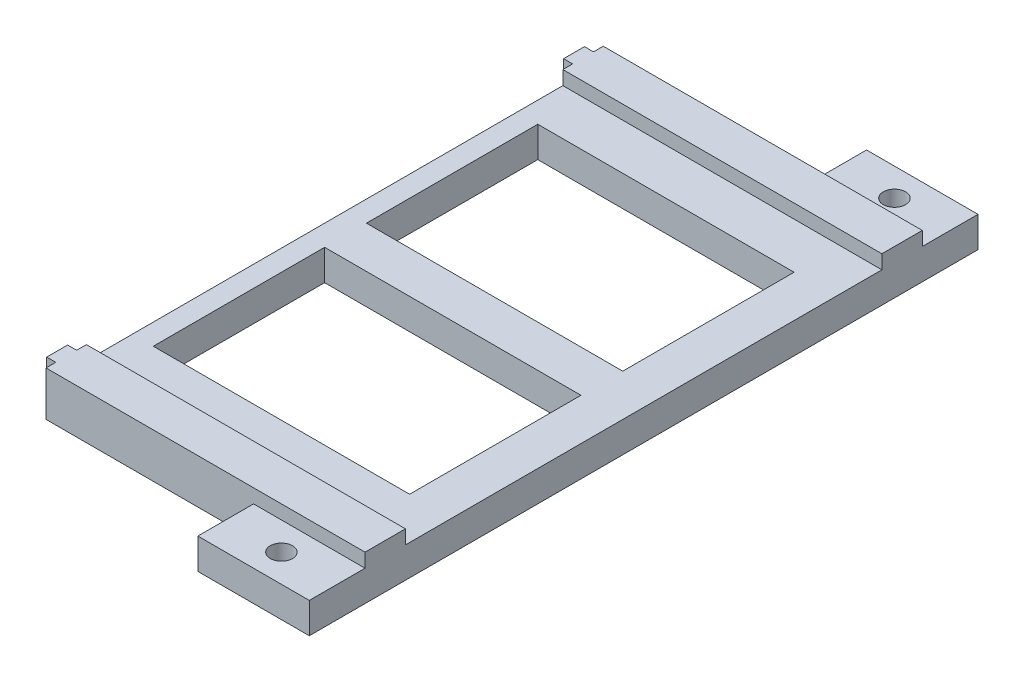
SolidWorks part; units mm, degrees
ref_plane "Front Plane" through (0, 0, 0) normal (0, 0, 1) x (1, 0, 0)
ref_plane "Top Plane" through (0, 0, 0) normal (0, 1, 0) x (1, 0, 0)
ref_plane "Right Plane" through (0, 0, 0) normal (1, 0, 0) x (0, 0, -1)
sketch "Sketch1" plane through (0, 0, 0) normal (0, 1, 0) x (1, 0, 0)
  line L1 (-184.5, -100) -> (184.5, -100)
  line L2 (-184.5, -100) -> (-184.5, 100)
  line L3 (-184.5, 100) -> (184.5, 100)
  line L4 (184.5, -100) -> (184.5, 100)
  line L5 (-184.5, -100) -> (184.5, 100) construction
  line L6 (-184.5, 100) -> (184.5, -100) construction
  point P0 (0, 0)
  dimension "D1" = 200
  dimension "353" = 369
extrude "Boss-Extrude1" add sketch "Sketch1" along normal blind 16
sketch "Sketch2" plane through (0, 16, 0) normal (0, 1, 0) x (1, 0, 0)
  line L0 (-184.5, -100) -> (184.5, -100) construction
  line L1 (-184.5, -100) -> (-155.6166, -100)
  line L2 (-184.5, -100) -> (-184.5, -36.5)
  line L3 (-184.5, -36.5) -> (-169.5, -36.5)
  line L4 (-169.5, -84) -> (-169.5, -36.5)
  line L5 (-184.5, 100) -> (-155.6166, 100)
  line L6 (-184.5, 100) -> (-184.5, 36.5)
  line L7 (-184.5, 36.5) -> (-169.5, 36.5)
  line L8 (-169.5, 84) -> (-169.5, 36.5)
  line L9 (-155.6166, 100) -> (-119.5, 100)
  line L11 (-169.5, 84) -> (-119.5, 84)
  line L12 (-119.5, 100) -> (-119.5, 84)
  line L13 (-155.6166, -100) -> (-119.5, -100)
  line L15 (-169.5, -84) -> (-119.5, -84)
  line L16 (-119.5, -100) -> (-119.5, -84)
  line L17 (-44.5, -100) -> (84.5, -100)
  line L18 (-44.5, -100) -> (-44.5, -84)
  line L19 (-44.5, -84) -> (84.5, -84)
  line L20 (84.5, -100) -> (84.5, -84)
  line L22 (-44.5, 100) -> (84.5, 100)
  line L23 (-44.5, 100) -> (-44.5, 84)
  line L24 (-44.5, 84) -> (84.5, 84)
  line L25 (84.5, 100) -> (84.5, 84)
  line L26 (184.5, -100) -> (184.5, 100) construction
  line L27 (184.5, 100) -> (-184.5, 100) construction
  point P28 (84.5, -92)
  dimension "D1" = 65
  dimension "D2" = 15
  dimension "D3" = 65
  dimension "D4" = 15
  dimension "D5" = 16
  dimension "D6" = 50
  dimension "D7" = 50
  dimension "D8" = 16
  dimension "D9" = 75
  dimension "D10" = 100
extrude "Boss-Extrude2" add sketch "Sketch2" along normal blind 12
sketch "Sketch3" plane through (0, 16, 0) normal (0, 1, 0) x (1, 0, 0)
  line L0 (-119.5, -84) -> (-169.5, -84) construction
  line L1 (-169.5, 84) -> (172.5, 84)
  line L2 (-169.5, 84) -> (-169.5, -84)
  line L3 (-169.5, -84) -> (172.5, -84)
  line L4 (172.5, 84) -> (172.5, -84)
  dimension "D1" = 342
extrude "Cut-Extrude1" cut sketch "Sketch3" against normal blind 5
sketch "Sketch4" plane through (0, 0, -100) normal (0, 0, -1) x (-1, 0, 0)
  line L0 (-84.5, 28) -> (44.5, 28) construction
  line L1 (-69.5, 16) -> (30.5, 16)
  line L2 (-69.5, 16) -> (-69.5, 28)
  line L3 (-69.5, 28) -> (30.5, 28)
  line L4 (30.5, 16) -> (30.5, 28)
  line L5 (-69.5, 16) -> (30.5, 28) construction
  line L6 (-69.5, 28) -> (30.5, 16) construction
  line L8 (-84.5, 28) -> (-84.5, 16) construction
  point P0 (-19.5, 22)
  dimension "D1" = 100
  dimension "D2" = 15
extrude "Boss-Extrude3" add sketch "Sketch4" along normal blind 60
sketch "Sketch8" plane through (0, 28, 0) normal (0, 1, 0) x (1, 0, 0)
  line L0 (-184.5, 36.5) -> (-169.5, 36.5)
  line L1 (-169.5, 36.5) -> (-169.5, 84)
  line L2 (-169.5, 84) -> (-119.5, 84)
  line L3 (-119.5, 84) -> (-119.5, 100)
  line L4 (-119.5, 100) -> (-184.5, 100)
  line L5 (-184.5, 100) -> (-184.5, 36.5)
extrude "Boss-Extrude5" add sketch "Sketch8" along normal blind 42
sketch "Sketch9" plane through (0, 70, 0) normal (0, 1, 0) x (1, 0, 0)
  line L0 (-119.5, 84) -> (-119.5, 70)
  line L1 (-119.5, 70) -> (-155.5, 70)
  line L2 (-155.5, 70) -> (-155.5, 35)
  line L3 (-155.5, 35) -> (-169.5, 35)
  line L4 (-169.5, 36.5) -> (-169.5, 84) construction
  line L5 (-169.5, 84) -> (-169.5, -84) construction
  line L6 (172.5, 84) -> (-169.5, 84) construction
  dimension "D1" = 14
  dimension "D2" = 14
extrude "Extrude-Thin1" add sketch "Sketch9" against normal blind 7 thin thin type one direction wall 10
sketch "Sketch11" plane through (0, 70, 0) normal (0, 1, 0) x (1, 0, 0)
  line L1 (-184.5, 100) -> (-44.5, 100)
  line L2 (-184.5, 100) -> (-184.5, -100)
  line L3 (-184.5, -100) -> (-44.5, -100)
  line L4 (-44.5, 100) -> (-44.5, -100)
extrude "Cut-Extrude5" cut sketch "Sketch11" against normal through all
sketch "Sketch13" plane through (0, 28, 0) normal (0, 1, 0) x (1, 0, 0)
  line L0 (-44.5, 96.22) -> (-44.5, 87.78)
  line L1 (-44.5, 100) -> (-44.5, 84) construction
  line L2 (-44.5, 87.78) -> (-52.3, 86.4046)
  line L3 (-52.3, 86.4046) -> (-52.3, 97.5954)
  line L4 (-52.3, 97.5954) -> (-44.5, 96.22)
  line L5 (-44.5, -87.78) -> (-44.5, -96.22)
  line L6 (-44.5, -96.22) -> (-52.5, -97.6306)
  line L7 (-52.5, -97.6306) -> (-52.5, -86.3694)
  line L8 (-52.5, -86.3694) -> (-44.5, -87.78)
  line L9 (-44.5, -84) -> (-44.5, -100) construction
  dimension "D1" = 3.78
  dimension "D2" = 3.78
  dimension "D3" = 7.8
  dimension "D4" = 80
  dimension "D5" = 80
  dimension "D6" = 3.78
  dimension "D7" = 3.78
  dimension "D8" = 80
  dimension "D9" = 8
  dimension "D10" = 80
extrude "Boss-Extrude6" add sketch "Sketch13" against normal through all
fillet "Fillet1" radius 1.5 8 edges at (-44.5, 14, 87.78) (-52.5, 14, 86.3694) (-52.5, 14, 97.6306) (-44.5, 14, 96.22) (-44.5, 14, -96.22) (-44.5, 14, -87.78) (-52.3, 14, -86.4046) (-52.3, 14, -97.5954)
sketch "Sketch14" plane through (0, 0, 0) normal (0, 0, 1) x (1, 0, 0)
  line L0 (84.5, 16) -> (184.5, 16) construction
  line L1 (84.5, 28) -> (-67.1004, 28)
  line L2 (84.5, 28) -> (84.5, 16)
  line L3 (84.5, 16) -> (-67.1004, 16)
  line L4 (-67.1004, 28) -> (-67.1004, 16)
extrude "Cut-Extrude6" cut sketch "Sketch14" along normal through all and the other way through all
sketch "Sketch15" plane through (0, 16, 0) normal (0, 1, 0) x (1, 0, 0)
  line L0 (184.5, 100) -> (-44.5, 100) construction
  line L1 (-17.9669, 100) -> (79.8991, 100)
  line L2 (-17.9669, 100) -> (-17.9669, 84)
  line L3 (-17.9669, 84) -> (79.8991, 84)
  line L4 (79.8991, 100) -> (79.8991, 84)
  line L5 (172.5, 84) -> (-44.5, 84) construction
extrude "Boss-Extrude7" add sketch "Sketch15" along normal blind 62
sketch "Sketch16" plane through (0, 0, -84) normal (0, 0, 1) x (1, 0, 0)
  line L0 (79.8991, 78) -> (79.8991, 16) construction
  line L1 (-17.9669, 78) -> (79.8991, 78)
  line L2 (-17.9669, 78) -> (-17.9669, 65)
  line L3 (-17.9669, 65) -> (79.8991, 65)
  line L4 (79.8991, 78) -> (79.8991, 65)
  line L5 (172.5, 11) -> (-44.5, 11) construction
  dimension "D1" = 54
extrude "Boss-Extrude8" add sketch "Sketch16" along normal blind 20
sketch "Sketch17" plane through (0, 65, 0) normal (0, -1, 0) x (1, 0, 0)
  line L0 (-17.9669, -64) -> (-17.9669, -84) construction
  line L1 (-17.9669, -71.2) -> (79.8991, -71.2)
  line L2 (-17.9669, -71.2) -> (-17.9669, -76.85)
  line L3 (-17.9669, -76.85) -> (79.8991, -76.85)
  line L4 (79.8991, -71.2) -> (79.8991, -76.85)
  line L5 (79.8991, -64) -> (79.8991, -84) construction
  line L6 (-17.9669, -84) -> (79.8991, -84) construction
  dimension "D1" = 5.65
  dimension "D2" = 7.15
extrude "Boss-Extrude9" add sketch "Sketch17" along normal blind 5
fillet "Fillet3" radius 1 2 edges at (30.9661, 60, -76.85) (30.9661, 60, -71.2)
sketch "Sketch18" plane through (0, 16, 0) normal (0, 1, 0) x (1, 0, 0)
  line L0 (184.5, -100) -> (184.5, 100) construction
  line L1 (172.5, 84) -> (184.5, 84)
  line L2 (172.5, 84) -> (172.5, -84)
  line L3 (172.5, -84) -> (184.5, -84)
  line L4 (184.5, 84) -> (184.5, -84)
  line L5 (-44.5, -84) -> (172.5, -84) construction
extrude "Cut-Extrude7" cut sketch "Sketch18" against normal blind 5
sketch "Sketch19" plane through (0, 0, -100) normal (0, 0, -1) x (-1, 0, 0)
  line L1 (0, 0) -> (-40, 0)
  line L2 (0, 0) -> (0, 11)
  line L3 (0, 11) -> (-40, 11)
  line L4 (-40, 0) -> (-40, 11)
  line L5 (-184.5, 0) -> (-144.5, 0)
  line L6 (-184.5, 0) -> (-184.5, 11)
  line L7 (-184.5, 11) -> (-144.5, 11)
  line L8 (-144.5, 0) -> (-144.5, 11)
  dimension "D1" = 11
  dimension "D2" = 11
  dimension "D3" = 40
  dimension "D4" = 40
extrude "Boss-Extrude10" add sketch "Sketch19" along normal blind 20
sketch "Sketch20" plane through (0, 11, 0) normal (0, 1, 0) x (1, 0, 0)
  line L0 (40, 120) -> (40, 100) construction
  line L1 (0, 120) -> (40, 120) construction
  line L2 (144.5, 120) -> (184.5, 120) construction
  line L3 (184.5, 120) -> (184.5, 100) construction
  circle A0 centre (164.5, 110) radius 4
  circle A1 centre (20, 110) radius 4
  dimension "D1" = 20
  dimension "D2" = 10
  dimension "D3" = 10
  dimension "D4" = 20
extrude "Cut-Extrude8" cut sketch "Sketch20" against normal through all
mirror "Mirror3" about plane through (0, 0, 0) normal (0, 0, 1) of "Cut-Extrude8", "Boss-Extrude10", "Boss-Extrude9", "Boss-Extrude7", "Boss-Extrude8", "Fillet3"
sketch "Sketch21" plane through (0, 11, 0) normal (0, 1, 0) x (1, 0, 0)
  line L1 (-29.5, 7.5) -> (62.5, 7.5)
  line L2 (-29.5, 7.5) -> (-29.5, 69)
  line L3 (-29.5, 69) -> (62.5, 69)
  line L4 (62.5, 7.5) -> (62.5, 69)
  line L5 (77.5, 69) -> (169.5, 69)
  line L6 (77.5, 69) -> (77.5, 7.5)
  line L7 (77.5, 7.5) -> (169.5, 7.5)
  line L8 (169.5, 69) -> (169.5, 7.5)
  line L9 (-44.5, -84) -> (-44.5, 84) construction
  line L10 (62.5, -7.5) -> (-29.5, -7.5)
  line L11 (62.5, -7.5) -> (62.5, -69)
  line L12 (62.5, -69) -> (-29.5, -69)
  line L13 (-29.5, -7.5) -> (-29.5, -69)
  line L14 (77.5, -7.5) -> (169.5, -7.5)
  line L15 (77.5, -7.5) -> (77.5, -69)
  line L16 (77.5, -69) -> (169.5, -69)
  line L17 (169.5, -7.5) -> (169.5, -69)
  line L18 (184.5, -84) -> (184.5, 84) construction
  line L19 (-44.5, -84) -> (184.5, -84) construction
  line L20 (184.5, 84) -> (79.8991, 84) construction
  line L21 (-17.9669, 84) -> (-44.5, 84) construction
  line L22 (-55, 0) -> (55, 0) construction
  dimension "D1" = 15
  dimension "D2" = 15
  dimension "D3" = 15
  dimension "D4" = 15
  dimension "D5" = 15
  dimension "D6" = 15
  dimension "D7" = 15
  dimension "D8" = 15
  dimension "D9" = 7.5
  dimension "D10" = 7.5
  dimension "D11" = 7.5
  dimension "D12" = 7.5
  dimension "D13" = 122
  dimension "D14" = 15
extrude "Cut-Extrude9" cut sketch "Sketch21" against normal through all
sketch "Sketch22" plane through (79.8991, 0, 0) normal (1, 0, 0) x (0, 0, -1)
  line L0 (-84, 11) -> (84, 11) construction
  line L1 (-84, 65) -> (-85.5, 65)
  line L2 (-84, 65) -> (-84, 11)
  line L3 (-84, 11) -> (-85.5, 11)
  line L4 (-85.5, 65) -> (-85.5, 11)
  dimension "D1" = 1.5
extrude "Cut-Extrude10" cut sketch "Sketch22" against normal through all both and the other way through all
mirror "Mirror4" about plane through (0, 0, 0) normal (0, 0, 1) of "Cut-Extrude10"
sketch "Sketch23" plane through (0, 78, 0) normal (0, 1, 0) x (1, 0, 0)
  line L0 (79.8991, -100) -> (-17.9669, -100) construction
  line L1 (79.8991, -64) -> (66.6759, -64)
  line L2 (79.8991, -64) -> (79.8991, -100)
  line L3 (79.8991, -100) -> (66.6759, -100)
  line L4 (66.6759, -64) -> (66.6759, -100)
extrude "Cut-Extrude11" cut sketch "Sketch23" against normal up to surface (62 mm away) up to face at (132.1995, 16, -92.75)
mirror "Mirror5" about plane through (0, 0, 0) normal (0, 0, 1) of "Cut-Extrude11"
sketch "Sketch24" plane through (0, 78, 0) normal (0, 1, 0) x (1, 0, 0)
  line L0 (77.5, 69) -> (77.5, 7.5) construction
  line L1 (-52.5, -122.0217) -> (70, -122.0217)
  line L2 (-52.5, -122.0217) -> (-52.5, 123.3832)
  line L3 (-52.5, 123.3832) -> (70, 123.3832)
  line L4 (70, -122.0217) -> (70, 123.3832)
  line L5 (-52.5, -95.843) -> (-52.5, -88.157) construction
  dimension "D1" = 7.5
extrude "Cut-Extrude12" cut sketch "Sketch24" against normal through all and the other way through all
sketch "Sketch25" plane through (0, 16, 0) normal (0, 1, 0) x (1, 0, 0)
  line L0 (70, -85.5) -> (70, -100) construction
  line L1 (70, -89) -> (66.75, -89)
  line L2 (70, -89) -> (70, -96.5)
  line L3 (70, -96.5) -> (66.75, -96.5)
  line L4 (66.75, -89) -> (66.75, -96.5)
  line L5 (70, -85.5) -> (184.5, -85.5) construction
  dimension "D1" = 7.5
  dimension "D2" = 3.5
  dimension "D3" = 3.25
extrude "Boss-Extrude11" add sketch "Sketch25" against normal up to surface (16 mm away) up to face at (135.875, 0, 0)
mirror "Mirror6" about plane through (0, 0, 0) normal (0, 0, 1) of "Boss-Extrude11"
equation "\"´7.25\"=7.35"
